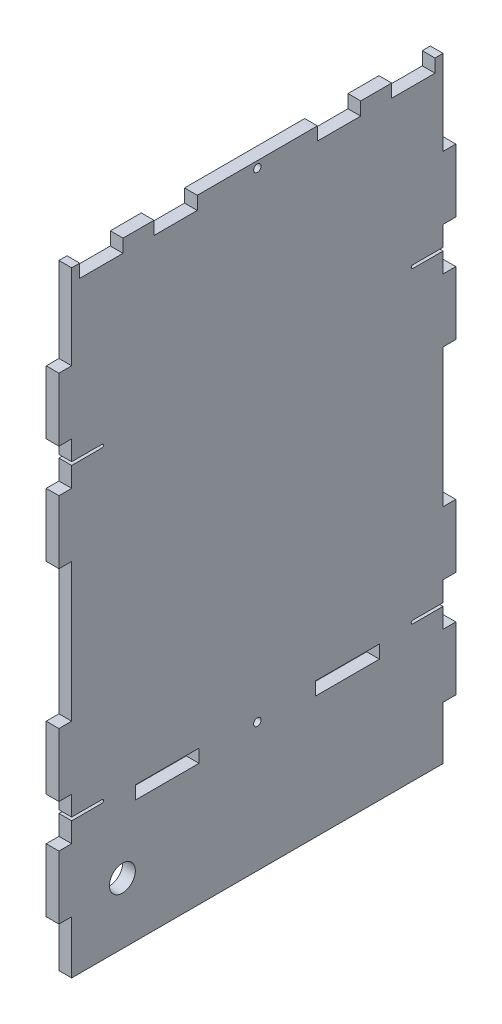
SolidWorks part; units mm, degrees
ref_plane "Plano frontal" through (0, 0, 0) normal (0, 0, 1) x (1, 0, 0)
ref_plane "Plano superior" through (0, 0, 0) normal (0, 1, 0) x (1, 0, 0)
ref_plane "Plano direito" through (0, 0, 0) normal (1, 0, 0) x (0, 0, -1)
sketch "Esboço1" plane through (0, 0, 0) normal (0, 0, 1) x (1, 0, 0)
  line L1 (0, 289) -> (6, 289)
  line L2 (0, 289) -> (0, 0)
  line L3 (0, 0) -> (6, 0)
  line L4 (6, 289) -> (6, 0)
  line L9 (0, 53.9) -> (6, 53.9)
  line L10 (0, 53.9) -> (0, 24.1)
  line L11 (0, 24.1) -> (6, 24.1)
  line L12 (6, 53.9) -> (6, 24.1)
  line L15 (6, 103.9) -> (6, 74.1)
  line L16 (0, 103.9) -> (0, 74.1)
  line L17 (0, 103.9) -> (6, 103.9)
  line L18 (0, 74.1) -> (6, 74.1)
  line L21 (0, 198.9) -> (6, 198.9)
  line L22 (6, 248.9) -> (6, 219.1)
  line L23 (0, 248.9) -> (0, 219.1)
  line L24 (6, 198.9) -> (6, 169.1)
  line L25 (0, 198.9) -> (0, 169.1)
  line L26 (0, 248.9) -> (6, 248.9)
  line L27 (0, 169.1) -> (6, 169.1)
  line L28 (0, 219.1) -> (6, 219.1)
  point P7 (3, 289)
  dimension "D1" = 6
  dimension "D2" = 289
  dimension "D3" = 20.2
  dimension "D4" = 29.8
  dimension "D5" = 29.8
  dimension "D6" = 65.2
  dimension "D7" = 40.1
  dimension "D8" = 29.8
  dimension "D9" = 20.2
  dimension "D11" = 24.1
extrude "Ressalto-extrusão3" add sketch "Esboço1" against normal blind 187 contours L2 L28 L4 L26 | L2 L27 L4 L21 | L2 L18 L4 L17 | L2 L11 L4 L9 region at (3, 234, 0) region at (3, 184, 0) region at (3, 89, 0) region at (3, 39, 0)
sketch "Esboço2" plane through (0, 0, 0) normal (-1, 0, 0) x (0, 0, 1)
  line L1 (-181, 288.9) -> (-6, 288.9)
  line L2 (-181, 288.9) -> (-181, -0.9)
  line L3 (-181, -0.9) -> (-6, -0.9)
  line L4 (-6, 288.9) -> (-6, -0.9)
  line L6 (0, 53.9) -> (0, 24.1) construction
  line L7 (-187, 24.1) -> (0, 24.1) construction
  line L8 (-187, 248.9) -> (-187, 219.1) construction
  line L9 (-187, 248.9) -> (0, 248.9) construction
  dimension "D1" = 6
  dimension "D2" = 25
  dimension "D3" = 6
  dimension "D4" = 40
extrude "Ressalto-extrusão4" add sketch "Esboço2" against normal blind 6
sketch "Esboço3" plane through (0, 0, 0) normal (-1, 0, 0) x (0, 0, 1)
  line L0 (-181, 209) -> (-6, 209) construction
  line L1 (-181, 219.1) -> (-181, 198.9) construction
  line L2 (-6, 198.9) -> (-6, 219.1) construction
  line L3 (-181, 64) -> (-6, 64) construction
  line L4 (-181, 74.1) -> (-181, 53.9) construction
  line L5 (-6, 53.9) -> (-6, 74.1) construction
  line L42 (-181, 208.25) -> (-6, 208.25)
  line L43 (-181, 63.25) -> (-6, 63.25)
  line L44 (-181, 209.75) -> (-6, 209.75)
  line L45 (-181, 64.75) -> (-6, 64.75)
  line L47 (-181, 209.75) -> (-6, 209.75)
  line L48 (-181, 209.75) -> (-181, 63.25)
  line L49 (-181, 63.25) -> (-6, 63.25)
  line L50 (-6, 209.75) -> (-6, 63.25)
  line L51 (-166, 209.75) -> (-21, 209.75)
  line L52 (-166, 209.75) -> (-166, 63.25)
  line L53 (-166, 63.25) -> (-21, 63.25)
  line L54 (-21, 209.75) -> (-21, 63.25)
  line M5 (-6, 53.9) -> (-6, 74.1)
  line M13 (-6, 198.9) -> (-6, 219.1)
  line M23 (-181, 219.1) -> (-181, 198.9)
  line M31 (-181, 74.1) -> (-181, 53.9)
  dimension "D3" = 15
  dimension "D4" = 15
  dimension "D1" = 0.75
  dimension "D2" = 0.75
extrude "Corte-extrusão1" cut sketch "Esboço3" against normal blind 6 contours L52 L45 L43 M31 | L45 L54 L43 M5 | L44 L54 L42 M13 | L52 L44 L42 M23 region at (0, 209, -173.5) region at (0, 209, -13.5) region at (0, 64, -173.5) region at (0, 64, -13.5)
sketch "Esboço4" plane through (0, 0, 0) normal (-1, 0, 0) x (0, 0, 1)
  line L0 (-138.5, 287.9) -> (-48.5, 281.7) construction
  line L1 (-168.5, 287.9) -> (-138.5, 287.9)
  line L2 (-168.5, 287.9) -> (-168.5, 281.7)
  line L3 (-168.5, 281.7) -> (-138.5, 281.7)
  line L4 (-138.5, 287.9) -> (-138.5, 281.7)
  line L5 (-48.5, 287.9) -> (-18.5, 287.9)
  line L6 (-48.5, 287.9) -> (-48.5, 281.7)
  line L7 (-48.5, 281.7) -> (-18.5, 281.7)
  line L8 (-18.5, 287.9) -> (-18.5, 281.7)
  line L9 (-6, 288.9) -> (-181, 288.9) construction
  circle A0 centre (-93.5, 284.8) radius 1.75
  point P12 (-93.5, 288.9)
  dimension "D3" = 3.5
  dimension "D1" = 30
  dimension "D2" = 6.2
  dimension "D4" = 90
  dimension "D5" = 1
extrude "Corte-extrusão2" [suppressed] cut sketch "Esboço4" against normal blind 22.8
sketch "Esboço5" plane through (0, 0, 0) normal (-1, 0, 0) x (0, 0, 1)
  line L1 (-151, 62.9) -> (-121, 62.9)
  line L2 (-151, 62.9) -> (-151, 56.7)
  line L3 (-151, 56.7) -> (-121, 56.7)
  line L4 (-121, 62.9) -> (-121, 56.7)
  line L6 (-181, -0.9) -> (-6, -0.9) construction
  line L7 (-121, 62.9) -> (-66, 56.7) construction
  line L8 (-66, 62.9) -> (-36, 62.9)
  line L9 (-66, 62.9) -> (-66, 56.7)
  line L10 (-66, 56.7) -> (-36, 56.7)
  line L11 (-36, 62.9) -> (-36, 56.7)
  circle A0 centre (-93.5, 59.8) radius 1.75
  dimension "D6" = 3.5
  dimension "D1" = 6.2
  dimension "D2" = 30
  dimension "D3" = 57.6
  dimension "D4" = 30
  dimension "D5" = 30
extrude "Corte-extrusão3" cut sketch "Esboço5" against normal blind 22.8
sketch "Esboço6" plane through (0, 0, 0) normal (-1, 0, 0) x (0, 0, 1)
  line L0 (-6, 288.9) -> (-181, 288.9) construction
  line L1 (-9.8, 288.9) -> (-30.2, 288.9)
  line L2 (-9.8, 288.9) -> (-9.8, 282.7)
  line L3 (-9.8, 282.7) -> (-30.2, 282.7)
  line L4 (-30.2, 288.9) -> (-30.2, 282.7)
  line L5 (-10, 282.9) -> (-10, 288.9) construction
  line L6 (-44.8, 288.9) -> (-65.2, 288.9)
  line L7 (-44.8, 288.9) -> (-44.8, 282.7)
  line L8 (-44.8, 282.7) -> (-65.2, 282.7)
  line L9 (-65.2, 288.9) -> (-65.2, 282.7)
  line L10 (-30, 282.9) -> (-30, 288.9) construction
  line L11 (-10, 282.9) -> (-30, 282.9) construction
  line L12 (-45, 282.9) -> (-45, 288.9) construction
  line L13 (-45, 282.9) -> (-65, 282.9) construction
  line L14 (-65, 282.9) -> (-65, 288.9) construction
  line L15 (-44.8, 288.9) -> (-30.2, 282.7) construction
  circle A0 centre (-37.5, 285.8) radius 1.75 construction
  dimension "D7" = 3.5
  dimension "D1" = 0.2
  dimension "D2" = 0.2
  dimension "D3" = 0.2
  dimension "D4" = 0.2
  dimension "D5" = 0.2
  dimension "D6" = 0.2
extrude "Corte-extrusão4" cut sketch "Esboço6" against normal blind 14.6
ref_plane "Plano1" through (0, 0, -93.5) normal (0, 0, 1) x (1, 0, 0)
mirror "Espelhar1" about plane through (0, 0, -93.5) normal (0, 0, 1) of "Corte-extrusão4"
fillet "Filete1" radius 0.75 8 edges at (3, 64.75, -166) (3, 63.25, -166) (3, 63.25, -21) (3, 64.75, -21) (3, 208.25, -21) (3, 209.75, -21) (3, 208.25, -166) (3, 209.75, -166)
sketch "Esboço7" plane through (0, 0, 0) normal (-1, 0, 0) x (0, 0, 1)
  line L0 (-121.8, 288.9) -> (-65.2, 282.7)
  circle A0 centre (-93.5, 285.8) radius 1.75
  dimension "D1" = 3.5
extrude "Corte-extrusão5" cut sketch "Esboço7" against normal blind 10 contours L0 A0 | L0 A0 region at (0, 286.5383, -93.4191) region at (0, 285.0617, -93.5809)
sketch "Esboço8" plane through (0, 0, 0) normal (-1, 0, 0) x (0, 0, 1)
  line L0 (-36, 56.7) -> (-36, -0.9) construction
  line L1 (-181, -0.9) -> (-6, -0.9) construction
  circle A0 centre (-29.9, 27.9) radius 6.1
  point P7 (-36, 27.9)
  point P8 (0, 0)
  point P9 (-29.3186, 27.8922)
  point P10 (0, 0)
  point P11 (-29.9, 34.5101)
  point P12 (-36, 27.9)
  dimension "D1" = 12.2
extrude "Corte-extrusão6" cut sketch "Esboço8" against normal blind 22
